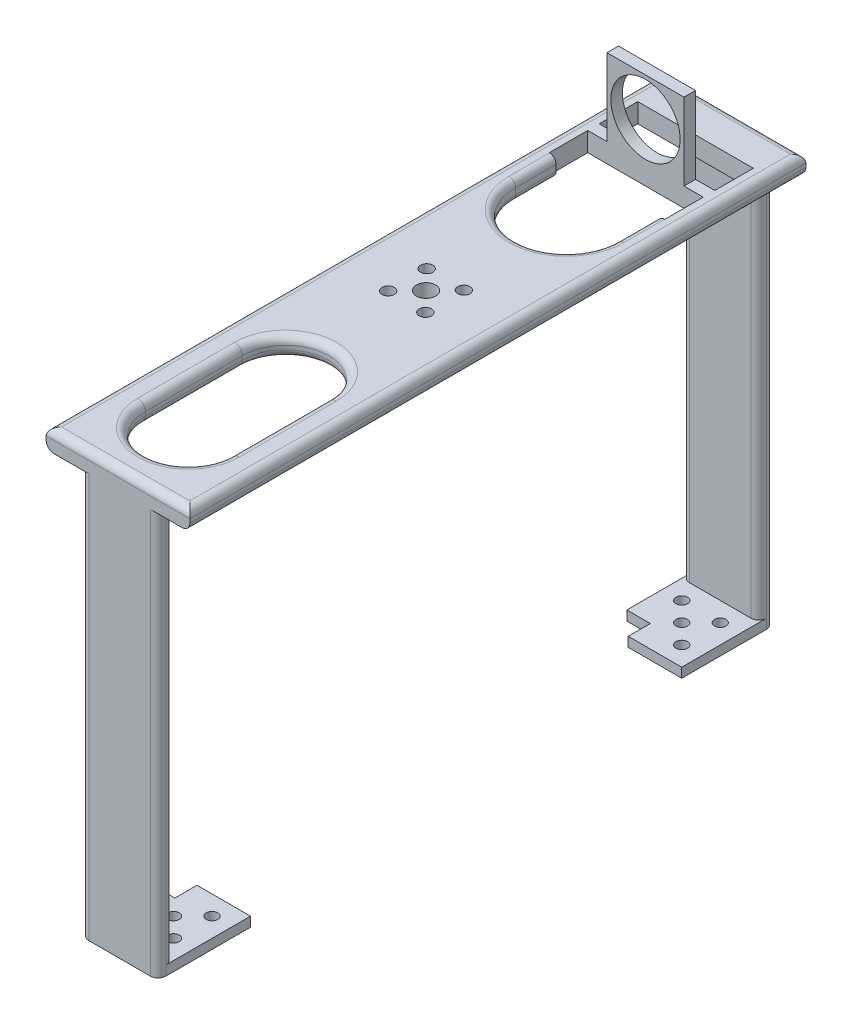
SolidWorks part; units mm, degrees
ref_plane "前视基准面" through (0, 0, 0) normal (0, 0, 1) x (1, 0, 0)
ref_plane "上视基准面" through (0, 0, 0) normal (0, 1, 0) x (1, 0, 0)
ref_plane "右视基准面" through (0, 0, 0) normal (1, 0, 0) x (0, 0, -1)
other "Configuration Table"
sketch "草图1" plane through (0, 0, 0) normal (0, 0, 1) x (1, 0, 0)
  line L0 (0, 0) -> (203, 0)
  line L1 (0, 0) -> (0, 2.5)
  line L2 (0, 2.5) -> (79, 2.5)
  line L6 (81.5, 2.5) -> (124, 2.5)
  line L11 (203, 2.5) -> (203, 0)
  line L12 (126.5, 2.5) -> (203, 2.5)
  line L13 (126.5, 2.5) -> (124, 2.5)
  line L14 (79, 2.5) -> (81.5, 2.5)
  dimension "D1" = 203
  dimension "D2" = 79
  dimension "D3" = 79
  dimension "D4" = 2.5
  dimension "D5" = 2.5
  dimension "D6" = 2.5
  dimension "D10" = 2.5
extrude "凸台-拉伸2" add sketch "草图1" along normal blind 160
sketch "草图10" plane through (0, 2.5, 0) normal (0, 1, 0) x (1, 0, 0)
  line L0 (101.5, 0) -> (101.5, -160) construction
  line L1 (203, 0) -> (0, 0) construction
  line L2 (203, -160) -> (0, -160) construction
  line L3 (0, -80) -> (203, -80) construction
  line L4 (0, -160) -> (0, 0) construction
  line L5 (203, -160) -> (203, 0) construction
sketch "草图20" plane through (0, 2.5, 0) normal (0, 1, 0) x (1, 0, 0)
  line L0 (203, 0) -> (0, 0) construction
  line L1 (57.115, 0) -> (77.115, 0)
  line L2 (57.115, 0) -> (57.115, -4)
  line L3 (57.115, -4) -> (77.115, -4)
  line L4 (77.115, 0) -> (77.115, -4)
  line L5 (0, -80) -> (203, -80)
  line L6 (57.115, -156) -> (77.115, -156)
  line L7 (77.115, -160) -> (77.115, -156)
  line L8 (57.115, -160) -> (77.115, -160)
  line L9 (57.115, -160) -> (57.115, -156)
  line M15 (0, -160) -> (203, -160)
  dimension "D1" = 20
  dimension "D2" = 4
extrude "凸台-拉伸5" add sketch "草图20" along normal blind 105 contours L9 L7 L6 M15 | L3 L4 L1 L2 region at (67.115, 2.5, 158)
sketch "草图23" plane through (0, 2.5, 0) normal (0, 1, 0) x (1, 0, 0)
  line L1 (48.2117, -131.7341) -> (63.2117, -131.7341)
  line L2 (48.2117, -131.7341) -> (48.2117, -141.7341)
  line L3 (48.2117, -141.7341) -> (63.2117, -141.7341)
  line L4 (63.2117, -131.7341) -> (63.2117, -141.7341)
  dimension "D1" = 15
  dimension "D2" = 10
sketch "草图24" plane through (0, 2.5, 0) normal (0, 1, 0) x (1, 0, 0)
  line L0 (77.115, -24) -> (57.115, -4) construction
  line L1 (57.115, -4) -> (77.115, -4)
  line L4 (77.115, -4) -> (77.115, -24)
  line L5 (77.115, -4) -> (57.115, -24) construction
  line L6 (67.115, -4) -> (67.115, -24) construction
  line L7 (57.115, -14) -> (77.115, -14) construction
  line L8 (0, -80) -> (203, -80) construction
  line L9 (63.2117, -136) -> (77.115, -136)
  line L10 (77.115, -156) -> (77.115, -136)
  line L11 (57.115, -156) -> (77.115, -156)
  line L12 (57.115, -156) -> (57.115, -141.7341)
  line L13 (63.2117, -141.7341) -> (63.2117, -136)
  line L14 (63.2117, -141.7341) -> (57.115, -141.7341)
  line L16 (57.115, -141.7341) -> (57.115, -136) construction
  line L17 (57.115, -136) -> (63.2117, -136) construction
  line L18 (57.115, -18.2659) -> (57.115, -24) construction
  line L19 (63.2117, -18.2659) -> (57.115, -18.2659)
  line L20 (63.2117, -18.2659) -> (63.2117, -24)
  line L21 (57.115, -24) -> (63.2117, -24) construction
  line L22 (57.115, -4) -> (57.115, -18.2659)
  line L23 (63.2117, -24) -> (77.115, -24)
  circle A1 centre (72.115, -9) radius 1.5
  circle A2 centre (67.115, -14) radius 1.5
  circle A3 centre (62.115, -9) radius 1.5
  circle A4 centre (72.115, -19) radius 1.5
  circle A6 centre (67.115, -146) radius 1.5
  circle A7 centre (72.115, -141) radius 1.5
  circle A8 centre (72.115, -151) radius 1.5
  circle A9 centre (62.115, -151) radius 1.5
  dimension "D3" = 5
  dimension "D4" = 3
  dimension "D5" = 3
  dimension "D1" = 20
  dimension "D2" = 20
  dimension "D6" = 14.2659
  dimension "D7" = 13.9033
extrude "凸台-拉伸7" add sketch "草图24" along normal blind 2.5
sketch "草图25" plane through (0, 0, 160) normal (0, 0, 1) x (1, 0, 0)
  line L1 (0, 2.5) -> (203, 2.5)
  line L2 (0, 2.5) -> (0, 0)
  line L3 (0, 0) -> (203, 0)
  line L4 (203, 2.5) -> (203, 0)
extrude "切除-拉伸16" cut sketch "草图25" against normal through all
sketch "草图27" plane through (0, 107.5, 0) normal (0, 1, 0) x (1, 0, 0)
  line L0 (67.115, -160) -> (215.1785, -160) construction
  line L1 (57.115, -160) -> (77.115, -160) construction
  line L2 (215.1785, -160) -> (-89.308, -160) construction
  line L3 (-35.0423, 0) -> (169.2724, 0) construction
  line L6 (85.3472, -160) -> (48.0424, -160)
  line L7 (85.3472, -160) -> (85.3472, 0)
  line L8 (85.3472, 0) -> (48.0424, 0)
  line L9 (48.0424, -160) -> (48.0424, 0)
  point P8 (67.115, 0)
extrude "凸台-拉伸8" add sketch "草图27" along normal blind 5
sketch "草图28" plane through (0, 112.5, 0) normal (0, 1, 0) x (1, 0, 0)
  line L0 (66.6948, -160) -> (66.6948, 0) construction
  line L1 (61.868, -75) -> (52.868, -75) construction
  line L2 (48.0424, -160) -> (85.3472, -160) construction
  line L3 (85.3472, 0) -> (48.0424, 0) construction
  line L4 (85.3472, -80) -> (48.0424, -80) construction
  line L5 (85.3472, -160) -> (85.3472, 0) construction
  line L6 (48.0424, 0) -> (48.0424, -160) construction
  line L8 (61.868, -75) -> (71.5217, -75) construction
  line L10 (61.868, -85) -> (71.5217, -85) construction
  line L11 (71.5217, -75) -> (71.5217, -85) construction
  line L12 (66.6948, -85) -> (66.6948, -75) construction
  line L13 (61.868, -80) -> (71.5217, -80) construction
  line L16 (66.6948, -141.6711) -> (66.6948, -116.4975) construction
  line L17 (77.9215, -141.6711) -> (77.9215, -116.4975)
  line L18 (55.4681, -141.6711) -> (55.4681, -116.4975)
  line L19 (61.868, -85) -> (52.868, -85) construction
  line L20 (52.868, -85) -> (61.868, -75) construction
  line L22 (61.8251, -80) -> (61.8251, -77.8006) construction
  circle A3 centre (61.868, -75) radius 1.6
  circle A4 centre (61.868, -85) radius 1.6
  arc A7 (77.9215, -141.6711) -> (55.4681, -141.6711) centre (66.6948, -141.6711) cw
  arc A8 (55.4681, -116.4975) -> (77.9215, -116.4975) centre (66.6948, -116.4975) cw
  circle A13 centre (66.6948, -80) radius 2.5
  circle A14 centre (71.5217, -75) radius 1.6
  circle A15 centre (71.5217, -85) radius 1.6
  point P30 (66.6948, -129.0843)
extrude "切除-拉伸17" cut sketch "草图28" against normal up to next
sketch "草图29" plane through (0, 112.5, 0) normal (0, 1, 0) x (1, 0, 0)
  line L0 (66.6948, 0) -> (66.6948, -20) construction
  line L1 (85.3472, 0) -> (48.0424, 0) construction
  line L2 (56.6948, -20) -> (76.6948, -20)
  line L3 (56.6948, -20) -> (56.6948, -23)
  line L4 (56.6948, -23) -> (76.6948, -23)
  line L5 (76.6948, -23) -> (76.6948, -20)
  point P7 (66.6948, -20)
extrude "凸台-拉伸9" add sketch "草图29" along normal blind 20
sketch "草图30" plane through (0, 0, 20) normal (0, 0, -1) x (-1, 0, 0)
  line L0 (-76.6948, 112.5) -> (-56.6948, 132.5) construction
  circle A0 centre (-66.6948, 122.5) radius 9
extrude "切除-拉伸18" cut sketch "草图30" against normal blind 3
sketch "草图31" plane through (0, 112.5, 0) normal (0, 1, 0) x (1, 0, 0)
  line L0 (66.6948, 0) -> (66.6948, -48.7582) construction
  line L1 (85.3472, 0) -> (48.0424, 0) construction
  line L2 (51.6948, -20) -> (81.6948, -20)
  line L4 (66.6948, -25) -> (69.6333, -25) construction
  line L6 (81.6948, -10) -> (51.6948, -10)
  line L7 (81.6948, -20) -> (81.6948, -10)
  line L11 (51.6948, -18) -> (51.6948, -35.3975) construction
  line L12 (51.6948, -35.3975) -> (66.6948, -35.3975) construction
  line L13 (51.6948, -10) -> (51.6948, -20)
  line L18 (56.6948, -23) -> (51.6948, -23) construction
  line L19 (51.6948, -23) -> (81.6948, -23)
  line L20 (81.6948, -23) -> (81.6948, -33)
  line L21 (81.6948, -33) -> (51.6948, -33)
  line L22 (51.6948, -33) -> (51.6948, -23)
  point P12 (66.6948, -18)
  point P15 (66.6948, -18)
  point P18 (66.6948, -25)
  point P19 (66.6948, -8)
  point P22 (81.6948, -18)
extrude "切除-拉伸19" cut sketch "草图31" against normal blind 5.6
fillet "圆角1" radius 2 6 edges at (48.0424, 107.5, 80) (85.3472, 107.5, 80) (85.3472, 112.5, 80) (48.0424, 112.5, 80) (66.6948, 112.5, 0) (66.6948, 112.5, 160)
fillet "圆角2" radius 2 8 edges at (57.115, 55, 160) (57.115, 56.25, 156) (77.115, 56.25, 156) (77.115, 55, 160) (77.115, 56.25, 4) (77.115, 55, 0) (57.115, 56.25, 4) (57.115, 55, 0)
fillet "圆角3" radius 2 8 edges at (66.6948, 107.5, 105.2709) (55.4681, 107.5, 129.0843) (66.6948, 107.5, 152.8978) (66.6948, 112.5, 152.8978) (55.4681, 112.5, 129.0843) (66.6948, 112.5, 105.2709) (77.9215, 107.5, 129.0843) (77.9215, 112.5, 129.0843)
sketch "草图32" plane through (0, 107.5, 0) normal (0, -1, 0) x (1, 0, 0)
  line L1 (10.3788, 190.6196) -> (126.5969, 190.6196)
  line L2 (10.3788, 190.6196) -> (10.3788, -46.0639)
  line L3 (10.3788, -46.0639) -> (126.5969, -46.0639)
  line L4 (126.5969, 190.6196) -> (126.5969, -46.0639)
ref_plane "基准面1" through (0, 0, 80) normal (0, 0, 1) x (1, 0, 0)
sketch "草图33" plane through (0, 112.5, 0) normal (0, 1, 0) x (1, 0, 0)
  line L0 (66.6948, -103.2709) -> (66.6948, -56.7291) construction
  line L1 (66.6948, -80) -> (113.8902, -80) construction
  line L2 (53.4681, -116.4975) -> (53.4681, -33) construction
  line L3 (51.6948, -33) -> (81.6948, -33) construction
  line L4 (53.4681, -43.5025) -> (53.4681, -33)
  line L5 (53.4681, -33) -> (79.9215, -33)
  line L6 (79.9215, -33) -> (79.9215, -43.5025)
  arc A0 (79.9215, -116.4975) -> (53.4681, -116.4975) centre (66.6948, -116.4975) ccw construction
  arc A1 (53.4681, -116.4975) -> (79.9215, -116.4975) centre (66.6948, -116.4975) cw construction
  arc A2 (53.4681, -43.5025) -> (79.9215, -43.5025) centre (66.6948, -43.5025) ccw
extrude "切除-拉伸20" cut sketch "草图33" against normal blind 10
fillet "圆角4" radius 1.7 6 edges at (53.4681, 107.5, 38.2512) (79.9215, 107.5, 38.2512) (53.4681, 112.5, 38.2512) (79.9215, 112.5, 38.2512) (66.6948, 107.5, 56.7291) (66.6948, 112.5, 56.7291)
